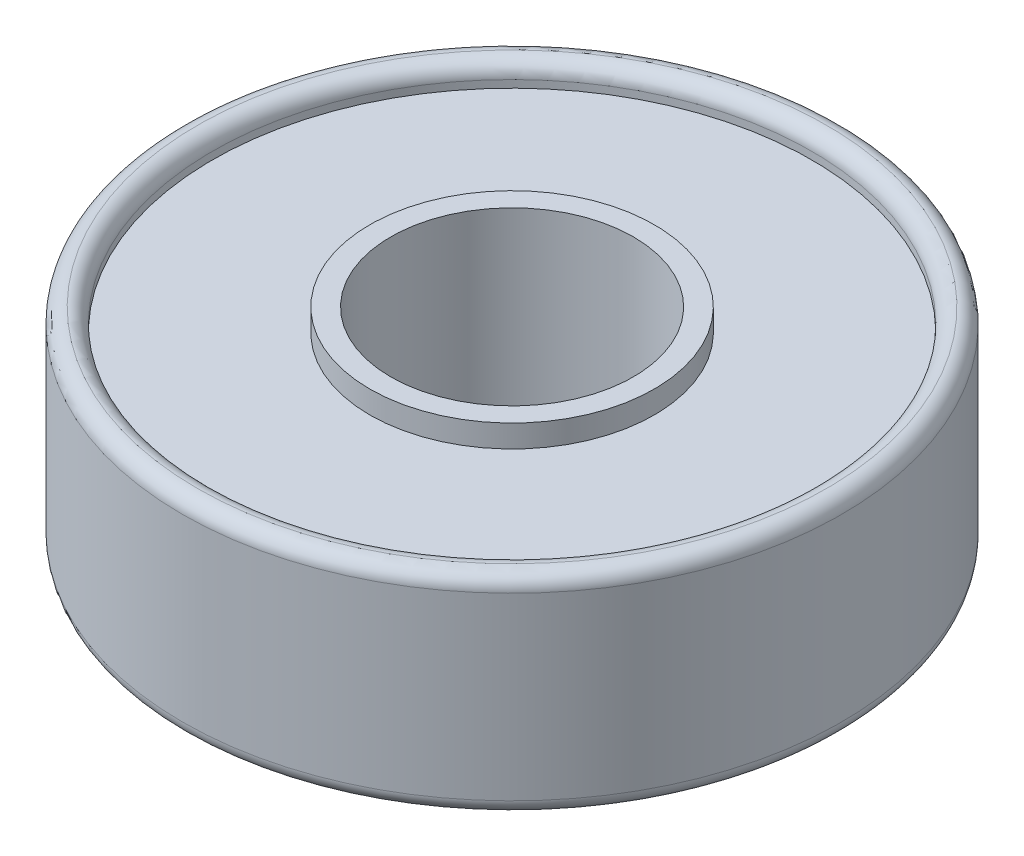
SolidWorks part; units mm, degrees
ref_plane "Front (XY)" through (0, 0, 0) normal (0, 0, 1) x (1, 0, 0)
ref_plane "Top (XZ)" through (0, 0, 0) normal (0, 1, 0) x (1, 0, 0)
ref_plane "Right (YZ)" through (0, 0, 0) normal (1, 0, 0) x (0, 0, -1)
sketch "Sketch1" plane through (0, 0, 0) normal (0, 1, 0) x (1, 0, 0)
  circle A0 centre (0, 0) radius 11
  dimension "D1" = 22
extrude "Boss-Extrude1" add sketch "Sketch1" along normal mid plane 7
sketch "Sketch2" plane through (0, 0, 0) normal (0, 1, 0) x (1, 0, 0)
  circle A2 centre (0, 0) radius 10
  circle A3 centre (0, 0) radius 10
  dimension "D1" = 1
extrude "Cut-Extrude1" cut sketch "Sketch2" against normal through all both and the other way through all
sketch "Sketch3" plane through (0, 0, 0) normal (0, 1, 0) x (1, 0, 0)
  circle A0 centre (0, 0) radius 10 construction
  circle A1 centre (0, 0) radius 10
extrude "Boss-Extrude2" add sketch "Sketch3" along normal mid plane 5.5
sketch "Sketch4" plane through (0, 0, 0) normal (0, 1, 0) x (1, 0, 0)
  circle A0 centre (0, 0) radius 4.75
  dimension "D1" = 9.5
extrude "Cut-Extrude2" cut sketch "Sketch4" against normal through all both and the other way through all
sketch "Sketch5" plane through (0, 0, 0) normal (0, 1, 0) x (1, 0, 0)
  circle A1 centre (0, 0) radius 4.75 construction
  circle A2 centre (0, 0) radius 4.75
extrude "Boss-Extrude3" add sketch "Sketch5" along normal mid plane 7
sketch "Sketch6" plane through (0, 0, 0) normal (0, 1, 0) x (1, 0, 0)
  circle A0 centre (0, 0) radius 4.05
  dimension "D1" = 8.1
extrude "Cut-Extrude3" cut sketch "Sketch6" against normal through all both and the other way through all
fillet "Fillet1" radius 0.5 4 edges at (0, -3.5, 11) (0, -3.5, 10) (0, 3.5, 11) (0, 3.5, 10)
